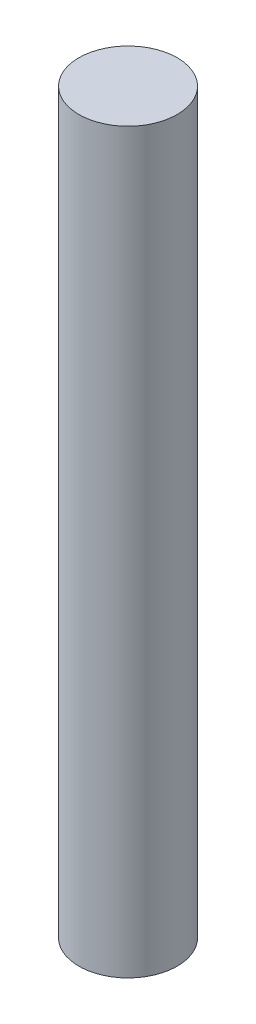
SolidWorks part; units mm, degrees
ref_plane "Front Plane" through (0, 0, 0) normal (0, 0, 1) x (1, 0, 0)
ref_plane "Top Plane" through (0, 0, 0) normal (0, 1, 0) x (1, 0, 0)
ref_plane "Right Plane" through (0, 0, 0) normal (1, 0, 0) x (0, 0, -1)
sketch "Sketch1" plane through (0, 0, 0) normal (0, 1, 0) x (1, 0, 0)
  circle A0 centre (0, 0) radius 4
extrude "Boss-Extrude1" add sketch "Sketch1" along normal blind 60
ref_axis "Axis1" through (0, 60, 0) along (0, -1, 0)
ref_axis "Axis2" through (0, 60, 0) along (0, -1, 0)
